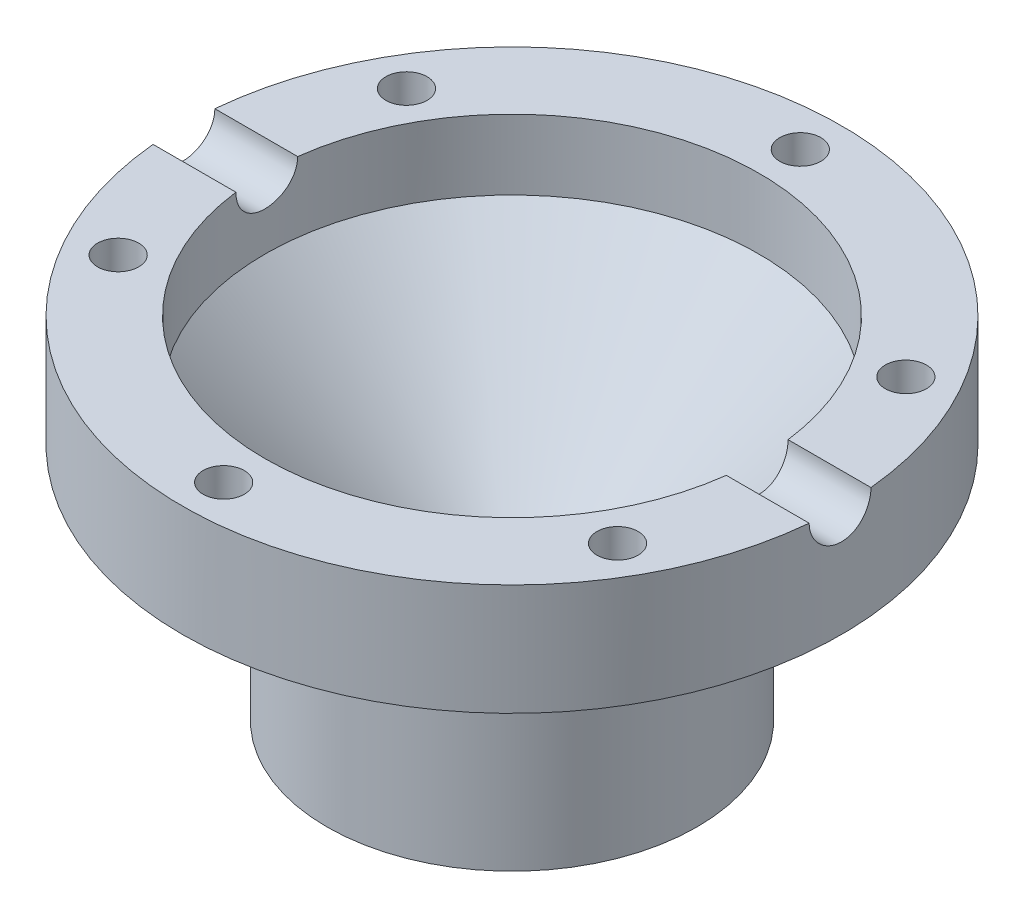
SolidWorks part; units mm, degrees
ref_plane "Front Plane" through (0, 0, 0) normal (0, 0, 1) x (1, 0, 0)
ref_plane "Top Plane" through (0, 0, 0) normal (0, 1, 0) x (1, 0, 0)
ref_plane "Right Plane" through (0, 0, 0) normal (1, 0, 0) x (0, 0, -1)
ref_axis "Centerline" through (0, 55, 0) along (0, -1, 0)
sketch "Sketch1" plane through (0, 0, 0) normal (0, 1, 0) x (1, 0, 0)
  circle A0 centre (0, 0) radius 20.32
  dimension "D1" = 40.64
extrude "Boss-Extrude1" add sketch "Sketch1" along normal blind 21.59
sketch "Sketch2" plane through (0, 0, 0) normal (0, 0, 1) x (1, 0, 0)
  line L0 (0, 26.2246) -> (0, -7.0612) construction
  line L5 (20.32, 21.59) -> (-20.32, 21.59) construction
  line L6 (0, 21.59) -> (-15.24, 21.59)
  line L7 (0, 21.59) -> (0, 17.272)
  line L8 (0, 17.272) -> (-15.24, 17.272)
  line L9 (-15.24, 21.59) -> (-15.24, 17.272)
  line L10 (-20.32, 21.59) -> (-20.32, 0) construction
  dimension "D1" = 5.08
  dimension "D2" = 4.318
revolve "Cut-Revolve1" cut sketch "Sketch2" angle 360 about axis through (0, 55, 0) along (0, -1, 0)
sketch "Sketch3" plane through (0, 0, 0) normal (0, 0, 1) x (1, 0, 0)
  line L0 (-20.32, 0) -> (20.32, 0) construction
  line L1 (-20.32, 14.732) -> (-15.24, 14.732)
  line L2 (-20.32, 14.732) -> (-20.32, 0)
  line L3 (-20.32, 0) -> (-15.24, 0)
  line L4 (-15.24, 14.732) -> (-15.24, 0)
  line L5 (20.32, 21.59) -> (-20.32, 21.59) construction
  line L6 (-20.32, 21.59) -> (-20.32, 0) construction
  point P8 (0, 0)
  dimension "D1" = 6.858
  dimension "D2" = 5.08
revolve "Cut-Revolve2" cut sketch "Sketch3" angle 360 about axis through (0, 55, 0) along (0, -1, 0)
sketch "Sketch4" plane through (0, 21.59, 0) normal (0, 1, 0) x (1, 0, 0)
  line L0 (0, 29.0947) -> (0, -35.1526) construction
  circle A0 centre (0, 17.78) radius 1.27
  dimension "D1" = 2.54
  dimension "D2" = 17.78
extrude "Cut-Extrude1" cut sketch "Sketch4" against normal up to next
pattern_circular "CirPattern1" count 6 over 360 about axis through (0, 55, 0) along (0, -1, 0) of "Cut-Extrude1"
sketch "Sketch5" plane through (0, 0, 0) normal (0, -1, 0) x (1, 0, 0)
  circle A0 centre (0, 0) radius 4.699
  dimension "D1" = 9.398
extrude "Cut-Extrude2" cut sketch "Sketch5" against normal up to next
sketch "Sketch7" plane through (0, 0, 0) normal (0, 0, 1) x (1, 0, 0)
  line L0 (-19.3213, 14.732) -> (23.1214, 14.732) construction
  line L1 (-20.32, 14.732) -> (20.32, 14.732) construction
  line L2 (-15.24, 14.732) -> (-15.24, 25.6293) construction
  line L4 (-15.24, 14.732) -> (-11.4097, 10.9017)
  line L5 (-11.4097, 10.9017) -> (-11.4097, 0)
  line L6 (-15.24, 0) -> (15.24, 0) construction
  line L7 (-11.4097, 0) -> (-15.24, 0)
  line L9 (-15.24, 14.732) -> (-15.24, 0)
  dimension "D1" = 45
  dimension "D2" = 10.9017
revolve "Cut-Revolve3" cut sketch "Sketch7" angle 360 about axis through (0, 55, 0) along (0, -1, 0)
sketch "Sketch8" plane through (0, 0, 0) normal (0, 0, 1) x (1, 0, 0)
  line L0 (-4.699, 24.8968) -> (-4.699, 18.7411) construction
  line L1 (-15.24, 24.5608) -> (-15.24, -3.2139) construction
  line L2 (15.24, 17.272) -> (-15.24, 17.272) construction
  line L3 (-4.699, 17.272) -> (-15.24, 17.272)
  line L4 (-15.24, 17.272) -> (-4.699, 6.731)
  line L5 (-22.2629, 0) -> (17.7783, 0) construction
  line L6 (-4.699, 6.731) -> (-4.699, 17.272)
  line L7 (-4.699, 17.272) -> (-4.699, -4.4972) construction
  dimension "D1" = 4.699
  dimension "D2" = 15.24
  dimension "D3" = 45
revolve "Cut-Revolve4" cut sketch "Sketch8" angle 360 about axis through (0, 55, 0) along (0, -1, 0)
ref_plane "Inlet Plane" through (20.32, 0, 0) normal (1, 0, 0) x (0, 0, -1)
sketch "Sketch9" plane through (20.32, 0, 0) normal (1, 0, 0) x (0, 0, -1)
  line L0 (0, 25.9244) -> (0, -6.8119) construction
  line L1 (20.32, 21.59) -> (-20.32, 21.59) construction
  circle A0 centre (0, 21.59) radius 1.905
  dimension "D1" = 3.81
extrude "Cut-Extrude3" cut sketch "Sketch9" against normal through all
